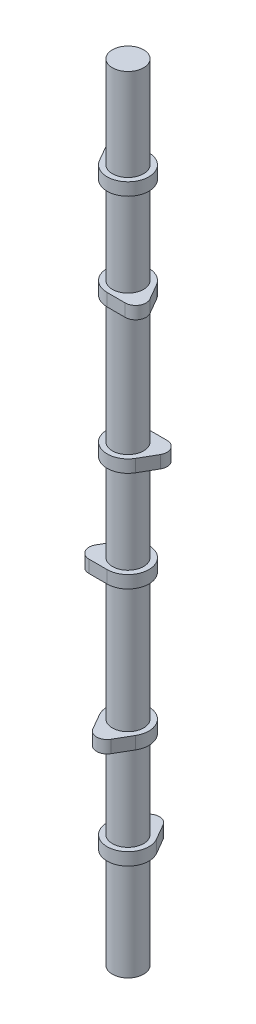
SolidWorks part; units mm, degrees
material "Gray Cast Iron"
ref_plane "Front Plane" through (0, 0, 0) normal (0, 0, 1) x (1, 0, 0)
ref_plane "Top Plane" through (0, 0, 0) normal (0, 1, 0) x (1, 0, 0)
ref_plane "Right Plane" through (0, 0, 0) normal (1, 0, 0) x (0, 0, -1)
sketch "Sketch1" plane through (0, 0, 0) normal (0, 1, 0) x (1, 0, 0)
  line L0 (-5.4993, 15.875) -> (-10.9985, 6.35)
  line L1 (5.4993, 15.875) -> (10.9985, 6.35)
  arc A0 (-10.9985, 6.35) -> (10.9985, 6.35) centre (0, 0) ccw
  arc A1 (5.4993, 15.875) -> (-5.4993, 15.875) centre (0, 12.7) ccw
  dimension "D1" = 25.4
  dimension "D2" = 12.7
extrude "Boss-Extrude1" add sketch "Sketch1" along normal mid plane 7.62
ref_axis "Axis1" through (0, 153.9226, 0) along (0, -1, 0)
move or copy body "Body-Move/Copy1" bodies to move or copy 101 copy yes number of copies 1 translate (0, 60.96, 0)
move or copy body "Body-Move/Copy2" bodies to move or copy 102 copy no rotation origin (0, 0, 0) rotation axis (0, 1, 0) rotation angle 180
sketch "Sketch2" plane through (0, 0, 0) normal (0, 1, 0) x (1, 0, 0)
  circle A0 centre (0, 0) radius 9.5
  dimension "D1" = 19
extrude "Boss-Extrude2" add sketch "Sketch2" along normal blind 146.05 and the other way blind 11.7 from offset 25.4 offset against normal yes
pattern_linear "LPattern1" count 3 spacing 146.05 along (0, 1, 0) of bodies 104
move or copy body "Body-Move/Copy3" bodies to move or copy 105 copy no rotation origin (0, 0, 0) rotation axis (0, 1, 0) rotation angle 120
move or copy body "Body-Move/Copy4" bodies to move or copy 106 copy no rotation origin (0, 0, 0) rotation axis (0, -1, 0) rotation angle 120
combine bodies "Combine1" operation type add bodies to combine 107 108 104
sketch "Sketch3" plane through (0, -37.1, 0) normal (0, -1, 0) x (1, 0, 0)
  circle A1 centre (0, 0) radius 9.5
  circle A2 centre (0, 0) radius 9.5
  dimension "D1" = 0
extrude "Boss-Extrude3" add sketch "Sketch3" along normal blind 27.94
